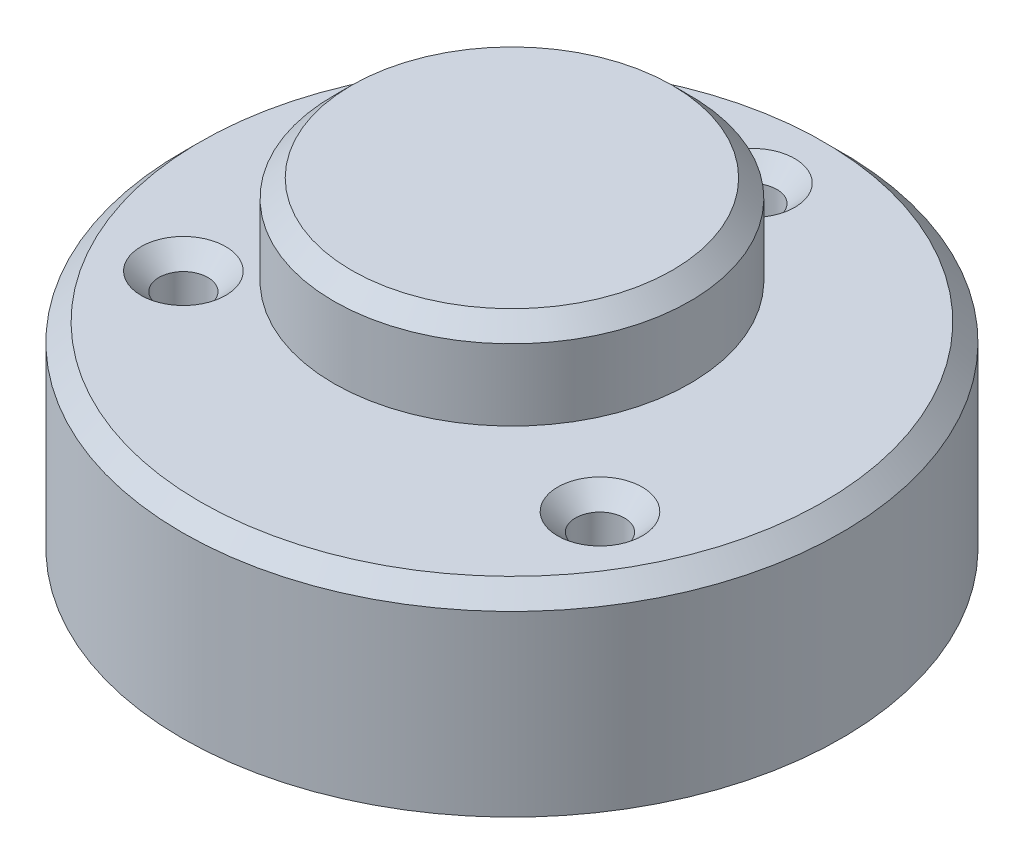
SolidWorks part; units mm, degrees
ref_plane "Front Plane" through (0, 0, 0) normal (0, 0, 1) x (1, 0, 0)
ref_plane "Top Plane" through (0, 0, 0) normal (0, 1, 0) x (1, 0, 0)
ref_plane "Right Plane" through (0, 0, 0) normal (1, 0, 0) x (0, 0, -1)
sketch "Sketch2" plane through (0, 0, 0) normal (0, 1, 0) x (1, 0, 0)
  line L0 (0, -13.5) -> (0, 13.5) construction
  line L1 (-11.6913, -6.75) -> (11.6913, 6.75) construction
  line L2 (-11.6913, 6.75) -> (11.6913, -6.75) construction
  circle A0 centre (0, 0) radius 18.5
  circle A1 centre (0, 13.5) radius 1.375
  circle A2 centre (0, -13.5) radius 1.375 construction
  circle A3 centre (-11.6913, 6.75) radius 1.375 construction
  circle A4 centre (-11.6913, -6.75) radius 1.375
  circle A5 centre (11.6913, -6.75) radius 1.375
  circle A6 centre (11.6913, 6.75) radius 1.375 construction
  circle A7 centre (0, 0) radius 13.5 construction
  point P6 (0, 0)
  point P11 (0, 0)
  point P14 (0, 0)
  dimension "D1" = 37
  dimension "D2" = 60
  dimension "D4" = 2.75
  dimension "D3" = 60
  dimension "D5" = 27
extrude "Boss-Extrude1" add sketch "Sketch2" along normal blind 11
sketch "Sketch4" plane through (0, 11, 0) normal (0, 1, 0) x (1, 0, 0)
  circle A0 centre (0, 0) radius 5
  dimension "D1" = 10
extrude "Boss-Extrude3" add sketch "Sketch4" along normal blind 2
sketch "Sketch5" plane through (0, 13, 0) normal (0, 1, 0) x (1, 0, 0)
  circle A0 centre (0, 0) radius 10
extrude "Boss-Extrude4" add sketch "Sketch5" along normal blind 5
fillet "Fillet1" radius 1 2 edges at (0, 13, 5) (0, 11, 5)
chamfer "Chamfer3" distance 1 angle 45 3 edges at (11.6913, 11, 8.125) (-11.6913, 11, 8.125) (0, 11, -12.125)
chamfer "Chamfer4" distance 1 angle 45 2 edges at (0, 11, 18.5) (0, 18, 10)
